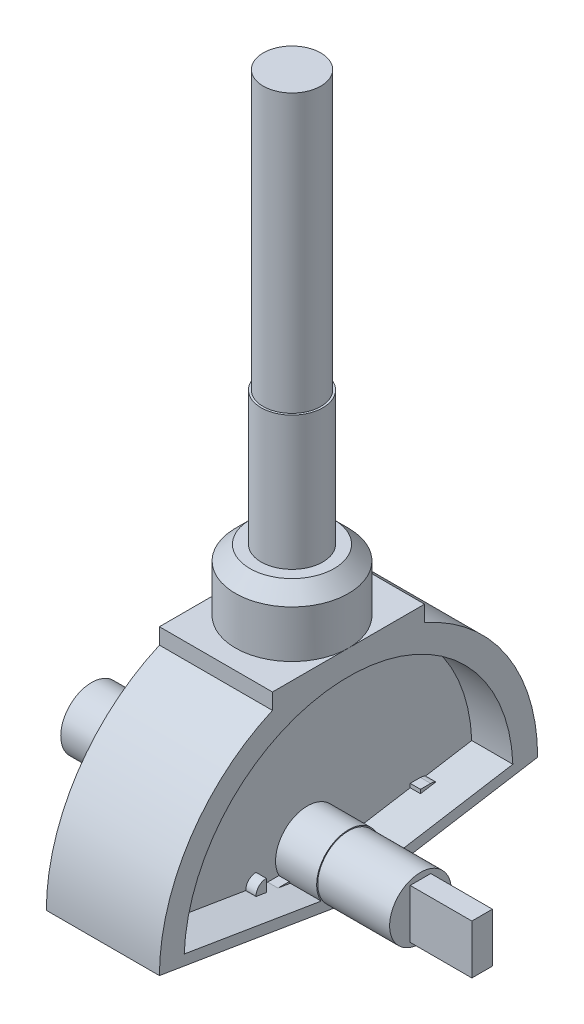
SolidWorks part; units mm, degrees
ref_plane "前视基准面" through (0, 0, 0) normal (0, 0, 1) x (1, 0, 0)
ref_plane "上视基准面" through (0, 0, 0) normal (0, 1, 0) x (1, 0, 0)
ref_plane "右视基准面" through (0, 0, 0) normal (1, 0, 0) x (0, 0, -1)
sketch "草图1" plane through (0, 0, 0) normal (1, 0, 0) x (0, 0, -1)
  line L0 (-9.2, 0) -> (-0.6302, -1.4161)
  line L1 (9.2, 0) -> (0.6302, -1.4161)
  arc A1 (9.2, 0) -> (-9.2, 0) centre (0, 0) ccw
  arc A3 (-0.6302, -1.4161) -> (0.6302, -1.4161) centre (0, 0) ccw
extrude "凸台-拉伸1" add sketch "草图1" along normal blind 5.5
sketch "草图2" plane through (5.5, 0, 0) normal (1, 0, 0) x (0, 0, -1)
  line L4 (-7.9941, 0.3075) -> (-1.3315, -0.7934)
  line L5 (1.3315, -0.7934) -> (7.9941, 0.3075)
  arc A0 (1.3315, -0.7934) -> (-1.3315, -0.7934) centre (0, 0) ccw
  arc A3 (7.9941, 0.3075) -> (-7.9941, 0.3075) centre (0, 0) ccw
  point P9 (-9.1185, 0.4933)
  point P10 (-0.5486, -0.9228)
  point P11 (0.5486, -0.9228)
  point P12 (9.1185, 0.4933)
extrude "切除-拉伸1" cut sketch "草图2" against normal blind 2
sketch "草图3" plane through (0, 0, 0) normal (-1, 0, 0) x (0, 0, 1)
  line L4 (-1.3315, -0.7934) -> (-7.9941, 0.3075)
  line L5 (7.9941, 0.3075) -> (1.3315, -0.7934)
  arc A0 (1.3315, -0.7934) -> (-1.3315, -0.7934) centre (0, 0) ccw
  arc A3 (7.9941, 0.3075) -> (-7.9941, 0.3075) centre (0, 0) ccw
  point P14 (9.1185, 0.4933)
  point P15 (0.5486, -0.9228)
extrude "切除-拉伸2" cut sketch "草图3" against normal blind 2
sketch "草图4" plane through (0, 0, 0) normal (-1, 0, 0) x (0, 0, 1)
  line L0 (0, 9.2) -> (-3.7, 9.2)
  line L1 (-3.7, 9.2) -> (-3.7, 8.4232)
  line L2 (-3.7, 8.4232) -> (3.7, 8.4232)
  line L3 (3.7, 8.4232) -> (3.7, 9.2)
  line L4 (3.7, 9.2) -> (0, 9.2)
  arc A0 (9.2, 0) -> (-9.2, 0) centre (0, 0) ccw construction
extrude "凸台-拉伸2" add sketch "草图4" against normal blind 5.5
sketch "草图5" plane through (0, 9.2, 0) normal (0, 1, 0) x (1, 0, 0)
  circle A0 centre (2.75, 0) radius 2.75
extrude "凸台-拉伸3" add sketch "草图5" along normal blind 3
fillet "倒角1" radius 0.7 1 edges at (2.75, 12.2, 2.75) type face fillet profile chamfer first side face at (2.75, 12.2, 2.75) second side face at (2.75, 12.2, 2.75)
sketch "草图6" plane through (0, 12.2, 0) normal (0, 1, 0) x (1, 0, 0)
  circle A0 centre (2.75, 0) radius 1.5
extrude "凸台-拉伸4" add sketch "草图6" along normal blind 20
sketch "草图7" plane through (0, 0, 0) normal (-1, 0, 0) x (0, 0, 1)
  circle A0 centre (0, 0) radius 1.5
extrude "凸台-拉伸5" add sketch "草图7" along normal blind 7
sketch "草图8" plane through (5.5, 0, 0) normal (1, 0, 0) x (0, 0, -1)
  circle A0 centre (0, 0) radius 1.5
extrude "凸台-拉伸6" add sketch "草图8" along normal blind 3.5
sketch "草图9" plane through (9, 0, 0) normal (1, 0, 0) x (0, 0, -1)
  line L1 (0, 1.2) -> (0.5, 1.2)
  line L2 (0.5, 1.2) -> (0.5, -1.2)
  line L3 (0.5, -1.2) -> (-0.5, -1.2)
  line L4 (-0.5, -1.2) -> (-0.5, 1.2)
  line L5 (-0.5, 1.2) -> (0, 1.2)
extrude "凸台-拉伸7" add sketch "草图9" along normal blind 3
ref_plane "基准面1" through (4, 0, 0) normal (1, 0, 0) x (0, 0, -1)
sketch "草图10" plane through (4, 0, 0) normal (1, 0, 0) x (0, 0, -1)
  line L0 (5.5, 0) -> (5, 0)
  line L1 (5, 0) -> (5, -0.694)
  line L2 (0, -2) -> (5.5, -2)
  line L3 (6, -1.5) -> (6, -0.5)
  line L4 (0, -2) -> (-2.5, -2)
  line L5 (-3, -1.5) -> (-3, -0.5)
  line L7 (0.6302, -1.4161) -> (9.2, 0) construction
  line L8 (5, -0.694) -> (-2.5, -0.694)
  line L9 (-2.5, -0.694) -> (-2.5, 0)
  arc A1 (-3, -0.5) -> (-2.5, 0) centre (-2.5, -0.5) cw
  arc A2 (-2.5, -2) -> (-3, -1.5) centre (-2.5, -1.5) cw
  arc A3 (5.5, -2) -> (6, -1.5) centre (5.5, -1.5) ccw
  arc A4 (5.5, 0) -> (6, -0.5) centre (5.5, -0.5) cw
  dimension "D1" = 0.5
extrude "凸台-拉伸8" add sketch "草图10" against normal blind 7.5
sketch "草图11" plane through (2, 0, 0) normal (-1, 0, 0) x (0, 0, 1)
  line L0 (-1.5, 0) -> (-1.5, 1.3229)
  line L1 (1.5, 1.3229) -> (1.5995, -1.2007)
  line L2 (-1.5, 0) -> (-1.5, -1.3229)
  arc A0 (-1.5, -1.3229) -> (1.5995, -1.2007) centre (0, 0) ccw
  circle A1 centre (0, 0) radius 1.5 construction
  arc A2 (1.3298, -0.694) -> (-1.3298, -0.694) centre (0, 0) ccw construction
  arc A3 (1.5, 1.3229) -> (-1.5, 1.3229) centre (0, 0) ccw
extrude "凸台-拉伸9" add sketch "草图11" along normal blind 6
sketch "草图12" plane through (0, 32.2, 0) normal (0, 1, 0) x (1, 0, 0)
  circle A0 centre (2.75, 0) radius 1.4
  circle A1 centre (2.75, 0) radius 2.3695
extrude "切除-拉伸3" cut sketch "草图12" against normal blind 13.5
